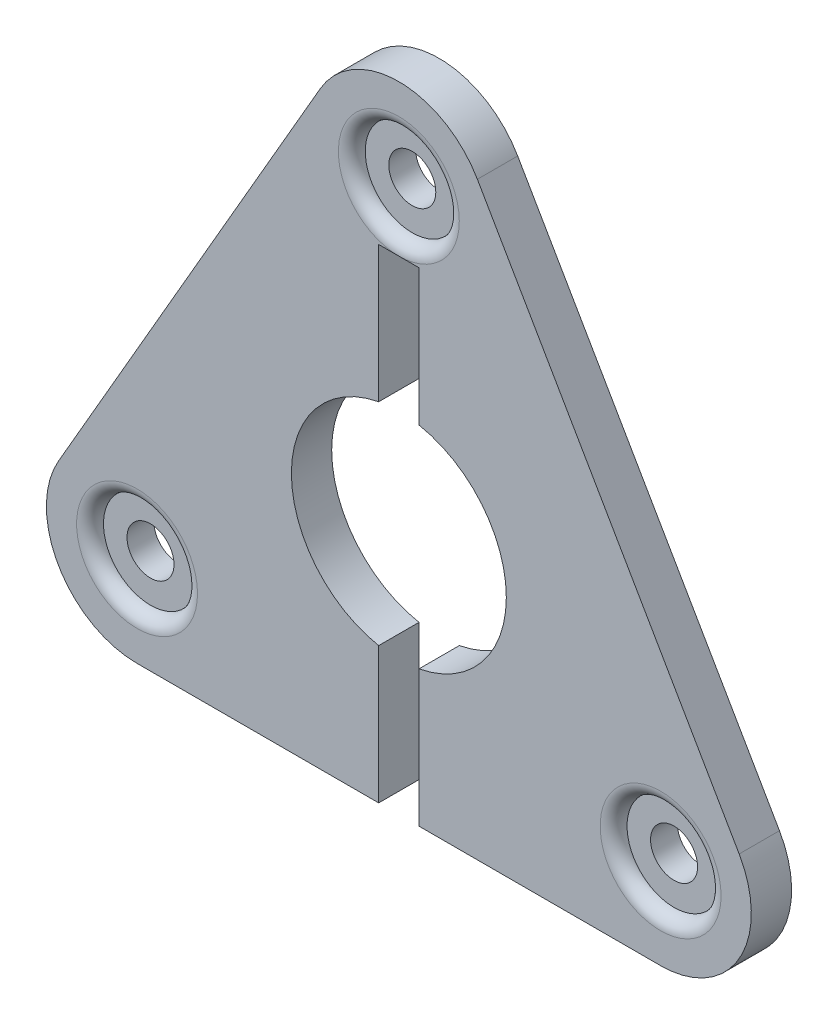
SolidWorks part; units mm, degrees
material "ABS"
ref_plane "Front Plane" through (0, 0, 0) normal (0, 0, 1) x (1, 0, 0)
ref_plane "Top Plane" through (0, 0, 0) normal (0, 1, 0) x (1, 0, 0)
ref_plane "Right Plane" through (0, 0, 0) normal (1, 0, 0) x (0, 0, -1)
sketch "Sketch1" plane through (0, 0, 0) normal (0, 0, 1) x (1, 0, 0)
  line L0 (0, 22.5) -> (0, 0) construction
  line L1 (0, 0) -> (19.4856, -11.25) construction
  line L2 (0, 0) -> (-19.4856, -11.25) construction
  line L3 (-25.3312, -7.875) -> (-5.8457, 25.875)
  line L4 (5.8457, 25.875) -> (25.3312, -7.875)
  line L5 (19.4856, -18) -> (-19.4856, -18)
  line L6 (-1.5, 18) -> (-1.5, 7.8581)
  line L7 (-1.5, 18) -> (1.5, 18)
  line L8 (1.5, 18) -> (1.5, 7.8581)
  line L9 (-1.5, 8) -> (1.5, 8) construction
  line L10 (1.5, -18) -> (1.5, -7.8581)
  line L11 (1.5, -18) -> (-1.5, -18)
  line L12 (-1.5, -18) -> (-1.5, -7.8581)
  circle A0 centre (0, 0) radius 22.5 construction
  circle A1 centre (0, 22.5) radius 1.75
  circle A2 centre (19.4856, -11.25) radius 1.75
  circle A3 centre (-19.4856, -11.25) radius 1.75
  arc A4 (-5.8457, 25.875) -> (5.8457, 25.875) centre (0, 22.5) cw
  arc A5 (25.3312, -7.875) -> (19.4856, -18) centre (19.4856, -11.25) cw
  arc A6 (-25.3312, -7.875) -> (-19.4856, -18) centre (-19.4856, -11.25) ccw
  circle A7 centre (0, 0) radius 8
  point P28 (0, 0)
  dimension "D3" = 5
  dimension "Screw_OD" = 3.5
  dimension "Screw_Circle_OD" = 45
  dimension "D4" = 2
  dimension "Shaft_Diameter" = 16
  dimension "D1" = 120
  dimension "D2" = 120
  dimension "Key_Height" = 10
  dimension "Key_Width" = 3
extrude "Boss-Extrude1" add sketch "Sketch1" along normal blind 3 contours L3 A6 L5 A5 L4 A4 A7 L6 L7 L8 A1 A2 A3 region at (-14.977, 8.6469, 0)
sketch "Sketch2" plane through (0, 0, 3) normal (0, 0, 1) x (1, 0, 0)
  circle A0 centre (0, 22.5) radius 3.5
  circle A1 centre (19.4856, -11.25) radius 3.5
  circle A2 centre (-19.4856, -11.25) radius 3.5
  dimension "D1" = 7
extrude "Cut-Extrude1" cut sketch "Sketch2" against normal blind 1
fillet "Fillet1" radius 1 3 edges at (-15.9856, -11.25, 3) (22.9856, -11.25, 3) (3.5, 22.5, 3)
